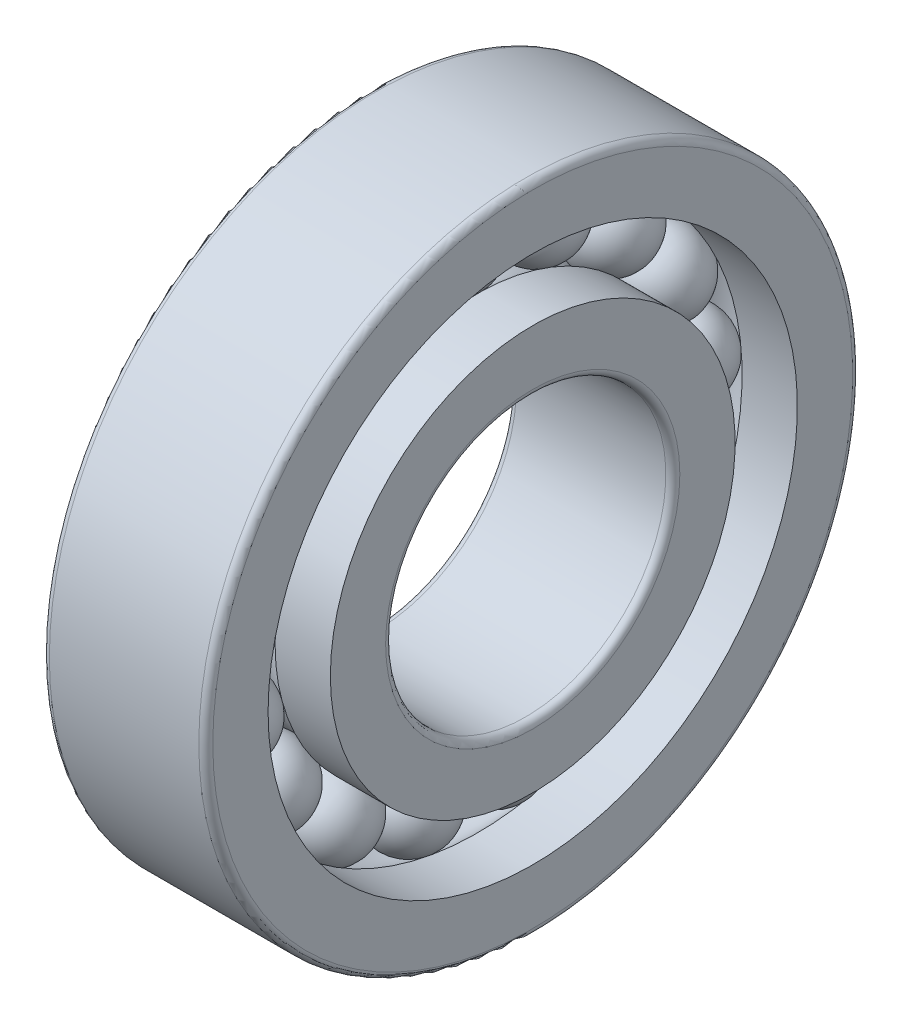
SolidWorks part; units mm, degrees
ref_plane "前视基准面" through (0, 0, 0) normal (0, 0, 1) x (1, 0, 0)
ref_plane "上视基准面" through (0, 0, 0) normal (0, 1, 0) x (1, 0, 0)
ref_plane "右视基准面" through (0, 0, 0) normal (1, 0, 0) x (0, 0, -1)
sketch "尺寸草图" plane through (0, 0, 0) normal (0, 0, 1) x (1, 0, 0)
  line L0 (-19.9271, 0) -> (19.9271, 0) construction
  line L1 (0, 21.603) -> (0, -21.603) construction
  line L2 (-3.2, 14) -> (3.2, 14)
  line L3 (3.5, 13.7) -> (3.5, 11.6333)
  line L4 (-3.5, 13.7) -> (-3.5, 11.6333)
  line L5 (-3.2, 11.3333) -> (3.2, 11.3333)
  line L6 (-3.5, 3.25) -> (3.3577, 3.25) construction
  line L7 (-3.2, 8.6667) -> (3.2, 8.6667)
  line L8 (3.5, 8.3667) -> (3.5, 6.3)
  line L9 (3.2, 6) -> (-3.2, 6)
  line L10 (-3.5, 6.3) -> (-3.5, 8.3667)
  line L11 (0, 3.25) -> (0, 11.75) construction
  line L13 (3.2, 11.3333) -> (3.2, 8.6667)
  line L14 (3.0333, 8.6667) -> (3.2579, 8.2778)
  line L15 (3.2579, 8.2778) -> (3.5, 8.2778)
  line L16 (3.4121, 11.4212) -> (3.4121, 8.5788)
  line L17 (0, 10) -> (-4.9155, 10) construction
  line L18 (-2.75, 11.6333) -> (-2.75, 11.3333)
  line L19 (-2.75, 11.3333) -> (-3.05, 11.0333)
  line L20 (-3.05, 11.0333) -> (-3.05, 8.9667)
  line L21 (-3.05, 8.9667) -> (-2.75, 8.6667)
  line L22 (-2.75, 8.6667) -> (-2.75, 8.3667)
  line L23 (-2.75, 11.6333) -> (-3.05, 11.6333)
  line L24 (-3.05, 11.6333) -> (-3.35, 11.3333)
  line L25 (-3.35, 11.3333) -> (-3.35, 8.6667)
  line L26 (-3.35, 8.6667) -> (-3.05, 8.3667)
  line L27 (-3.05, 8.3667) -> (-2.75, 8.3667)
  arc A1 (3.5, 11.6333) -> (3.2, 11.3333) centre (3.2, 11.6333) cw
  arc A2 (3.5, 8.3667) -> (3.2, 8.6667) centre (3.2, 8.3667) ccw
  arc A3 (-3.2, 8.6667) -> (-3.5, 8.3667) centre (-3.2, 8.3667) ccw
  arc A4 (-3.2, 11.3333) -> (-3.5, 11.6333) centre (-3.2, 11.6333) cw
  arc A5 (-3.2, 6) -> (-3.5, 6.3) centre (-3.2, 6.3) cw
  arc A6 (3.2, 6) -> (3.5, 6.3) centre (3.2, 6.3) ccw
  arc A7 (3.5, 13.7) -> (3.2, 14) centre (3.2, 13.7) ccw
  arc A8 (-3.2, 14) -> (-3.5, 13.7) centre (-3.2, 13.7) ccw
  circle A9 centre (0, 10) radius 1.75
  point P7 (0, 0)
  point P25 (-3.5, 8.6667)
  point P28 (-3.5, 11.3333)
  point P31 (-3.5, 6)
  point P36 (3.5, 14)
  point P39 (-3.5, 14)
  dimension "r" = 0.3
  dimension "D4" = 0.3
  dimension "D2" = 3.5
  dimension "B" = 7
  dimension "D3" = 0.3
  dimension "D" = 28
  dimension "(d)" = 12
  dimension "D5" = 3.25
  dimension "D6" = 2.6667
  dimension "D8" = 0.3889
  dimension "D9" = 60
  dimension "D10" = 0.4667
  dimension "D11" = 45
  dimension "D12" = 0.3
  dimension "D13" = 0.15
sketch "草图2" plane through (0, 0, 0) normal (0, 0, 1) x (1, 0, 0)
  line L0 (-3.35, 8.6667) -> (-3.5, 8.6667)
  line L1 (-3.5, 11.3333) -> (-3.35, 11.3333)
  line L2 (3.5, 8.3667) -> (3.5, 6.3) construction
  line L3 (-3.2, 8.6667) -> (3.2, 8.6667) construction
  line L4 (3.5, 8.3667) -> (3.5, 6.3)
  line L5 (-3.2, 11.3333) -> (3.2, 11.3333) construction
  line L6 (3.2, 6) -> (-3.2, 6) construction
  line L7 (1.1335, 11.3333) -> (3.5, 11.3333)
  line L9 (-3.5, 8.6667) -> (-3.5, 8.3667)
  line L10 (-3.2, 14) -> (3.2, 14) construction
  line L12 (1.1335, 8.6667) -> (3.2, 8.6667)
  line L14 (3.2, 6) -> (-3.2, 6)
  line L15 (-3.5, 6.3) -> (-3.5, 8.3667) construction
  line L16 (3.2, 8.6667) -> (3.5, 8.6667)
  line L17 (3.5, 8.6667) -> (3.5, 8.3667)
  line L18 (-3.5, 0) -> (3.5, 0) construction
  line L19 (-19.9271, 0) -> (19.9271, 0) construction
  line L20 (-3.5, 13.7) -> (-3.5, 11.3333)
  line L21 (-3.5, 13.7) -> (-3.5, 11.6333) construction
  line L22 (-3.2, 14) -> (3.2, 14)
  line L23 (3.5, 13.7) -> (3.5, 11.3333)
  line L24 (3.5, 13.7) -> (3.5, 11.6333) construction
  line L25 (-3.05, 11.6333) -> (-3.35, 11.3333) construction
  line L26 (-3.5, 6.3) -> (-3.5, 8.3667)
  line L27 (-2.75, 11.6333) -> (-3.05, 11.6333) construction
  line L28 (-2.75, 11.6333) -> (-2.75, 11.3333) construction
  line L29 (-3.35, 8.6667) -> (-3.05, 8.3667) construction
  line L30 (-3.05, 8.3667) -> (-2.75, 8.3667) construction
  line L31 (-2.75, 8.6667) -> (-2.75, 8.3667) construction
  line L32 (-3.05, 11.6333) -> (-3.35, 11.3333)
  line L33 (-2.75, 11.6333) -> (-3.05, 11.6333)
  line L34 (-2.75, 11.6333) -> (-2.75, 11.3333)
  line L35 (-3.35, 8.6667) -> (-3.05, 8.3667)
  line L36 (-3.05, 8.3667) -> (-2.75, 8.3667)
  line L37 (-2.75, 8.6667) -> (-2.75, 8.3667)
  line L38 (-2.75, 11.3333) -> (-1.1335, 11.3333)
  line L39 (-2.75, 8.6667) -> (-1.1335, 8.6667)
  arc A2 (1.1335, 11.3333) -> (-1.1335, 11.3333) centre (0, 10) ccw
  arc A3 (-3.2, 14) -> (-3.5, 13.7) centre (-3.2, 13.7) ccw construction
  arc A5 (3.5, 13.7) -> (3.2, 14) centre (3.2, 13.7) ccw construction
  arc A8 (3.2, 6) -> (3.5, 6.3) centre (3.2, 6.3) ccw construction
  arc A10 (-3.5, 6.3) -> (-3.2, 6) centre (-3.2, 6.3) ccw construction
  arc A11 (-3.2, 14) -> (-3.5, 13.7) centre (-3.2, 13.7) ccw
  arc A13 (3.5, 13.7) -> (3.2, 14) centre (3.2, 13.7) ccw
  arc A16 (3.2, 6) -> (3.5, 6.3) centre (3.2, 6.3) ccw
  arc A18 (-3.5, 6.3) -> (-3.2, 6) centre (-3.2, 6.3) ccw
  arc A19 (-1.1335, 8.6667) -> (1.1335, 8.6667) centre (0, 10) ccw
  circle A22 centre (0, 10) radius 1.75 construction
revolve "旋转1" add sketch "草图2" angle 360 about L18
sketch "草图3" plane through (0, 0, 0) normal (0, 0, 1) x (1, 0, 0)
  line L0 (-1.75, 10) -> (1.75, 10)
  line L1 (1.75, 10) -> (5.061, 10) construction
  circle A1 centre (0, 10) radius 1.75 construction
  arc A2 (1.75, 10) -> (-1.75, 10) centre (0, 10) ccw
revolve "旋转2" add sketch "草图3" angle 360 mid plane about L1 region at (0, 10.7427, 0)
sketch "草图4" plane through (0, 0, 0) normal (0, 0, 1) x (1, 0, 0)
  line L0 (-3.35, 11.3333) -> (-3.35, 8.6667) construction
  line L1 (-3.05, 11.6333) -> (-3.35, 11.3333) construction
  line L2 (-2.75, 11.6333) -> (-3.05, 11.6333) construction
  line L3 (-2.75, 11.6333) -> (-2.75, 11.3333) construction
  line L4 (-2.75, 11.3333) -> (-3.05, 11.0333) construction
  line L5 (-3.05, 11.0333) -> (-3.05, 8.9667) construction
  line L6 (-3.05, 8.9667) -> (-2.75, 8.6667) construction
  line L7 (-3.35, 8.6667) -> (-3.05, 8.3667) construction
  line L8 (-3.05, 8.3667) -> (-2.75, 8.3667) construction
  line L9 (-2.75, 8.6667) -> (-2.75, 8.3667) construction
  line L10 (-19.9271, 0) -> (19.9271, 0) construction
  line L11 (-3.35, 11.3333) -> (-3.35, 8.6667)
  line L12 (-3.05, 11.6333) -> (-3.35, 11.3333)
  line L13 (-2.75, 11.6333) -> (-3.05, 11.6333)
  line L14 (-2.75, 11.6333) -> (-2.75, 11.3333)
  line L15 (-2.75, 11.3333) -> (-3.05, 11.0333)
  line L16 (-3.05, 11.0333) -> (-3.05, 8.9667)
  line L17 (-3.05, 8.9667) -> (-2.75, 8.6667)
  line L18 (-3.35, 8.6667) -> (-3.05, 8.3667)
  line L19 (-3.05, 8.3667) -> (-2.75, 8.3667)
  line L20 (-2.75, 8.6667) -> (-2.75, 8.3667)
  line L21 (-19.9271, 0) -> (19.9271, 0) construction
revolve "旋转3" add sketch "草图4" angle 360 mid plane about L21
ref_axis "基准轴1" through (9.9, 0, 0) along (-1, 0, 0)
pattern_circular "阵列(圆周)5" count 17 over 360 about axis through (9.9, 0, 0) along (-1, 0, 0) of bodies 228 103
